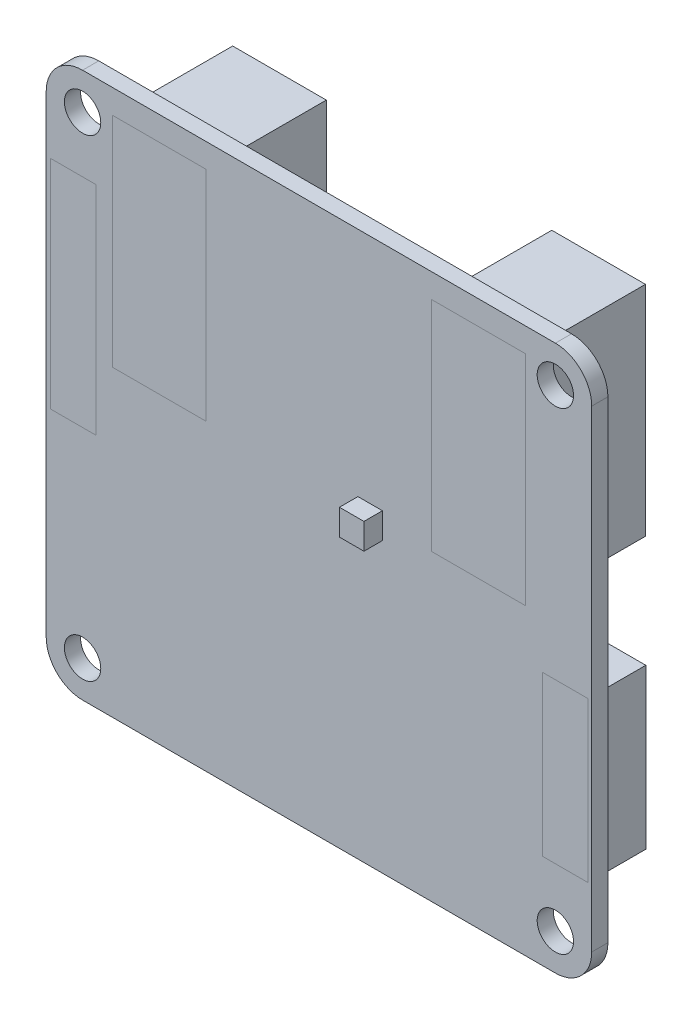
SolidWorks part; units mm, degrees
ref_plane "Front Plane" through (0, 0, 0) normal (0, 0, 1) x (1, 0, 0)
ref_plane "Top Plane" through (0, 0, 0) normal (0, 1, 0) x (1, 0, 0)
ref_plane "Right Plane" through (0, 0, 0) normal (1, 0, 0) x (0, 0, -1)
sketch "Sketch1" plane through (0, 0, 0) normal (0, 0, 1) x (1, 0, 0)
  line L1 (0, 0) -> (60, 0)
  line L2 (0, 0) -> (0, 60)
  line L3 (0, 60) -> (60, 60)
  line L4 (60, 0) -> (60, 60)
  line L5 (7.3, 57.35) -> (17.6, 57.35)
  line L6 (7.3, 57.35) -> (7.3, 33.35)
  line L7 (7.3, 33.35) -> (17.6, 33.35)
  line L8 (17.6, 57.35) -> (17.6, 33.35)
  line L9 (0.4948, 49.84) -> (5.4948, 49.84)
  line L10 (42.4, 57.35) -> (52.7, 57.35)
  line L11 (42.4, 57.35) -> (42.4, 33.35)
  line L12 (42.4, 33.35) -> (52.7, 33.35)
  line L13 (52.7, 57.35) -> (52.7, 33.35)
  line L14 (34.2841, 34.5273) -> (36.9775, 34.5273)
  line L15 (34.2841, 34.5273) -> (34.2841, 31.6832)
  line L16 (34.2841, 31.6832) -> (36.9775, 31.6832)
  line L17 (36.9775, 34.5273) -> (36.9775, 31.6832)
  line L18 (0.4948, 49.84) -> (0.4948, 25.964)
  line L19 (0.4948, 25.964) -> (5.4948, 25.964)
  line L20 (5.4948, 49.84) -> (5.4948, 25.964)
  line L21 (54.5954, 27.94) -> (59.5954, 27.94)
  line L22 (54.5954, 27.94) -> (54.5954, 10.414)
  line L23 (54.5954, 10.414) -> (59.5954, 10.414)
  line L24 (59.5954, 27.94) -> (59.5954, 10.414)
  arc A0 (0, 4) -> (4, 0) centre (4, 4) ccw
  circle A1 centre (4, 4) radius 2
  arc A2 (4, 60) -> (0, 56) centre (4, 56) ccw
  circle A3 centre (4, 56) radius 2
  arc A4 (60, 56) -> (56, 60) centre (56, 56) ccw
  circle A5 centre (56, 56) radius 2
  arc A6 (56, 0) -> (60, 4) centre (56, 4) ccw
  circle A7 centre (56, 4) radius 2
  circle A8 centre (4, 4) radius 4 construction
  circle A9 centre (56, 4) radius 4 construction
  circle A10 centre (56, 56) radius 4 construction
  circle A11 centre (4, 56) radius 4 construction
  point P7 (30, 30)
  point P9 (30, 0)
  point P10 (0, 30)
  point P23 (30, 30)
  dimension "D3" = 8
  dimension "D4" = 4
  dimension "D1" = 60
  dimension "D2" = 60
  dimension "D6" = 10.3
  dimension "D7" = 24
  dimension "D8" = 7.3
  dimension "D9" = 2.65
  dimension "D10" = 7.3
  dimension "D11" = 17.526
  dimension "D12" = 5
  dimension "D13" = 10.414
  dimension "D14" = 23.876
  dimension "D15" = 5
  dimension "D16" = 10.16
  dimension "D5" = 4
extrude "Boss-Extrude1" add sketch "Sketch1" along normal blind 1.778 contours L1 A6 L4 A4 L3 A2 L2 A0 A7 A5 A3 A1 L5 L8 L7 L6 L10 L13 L12 L11 L14 L17 L16 L15 L9 L20 L19 L18 L21 L24 L23 L22 region at (30.2852, 27.3088, 0)
extrude "Boss-Extrude2" add sketch "Sketch1<3>" against normal blind 11.43 and the other way up to surface (1.778 mm away) separate body contours L13 L10 L11 L12 | L8 L5 L6 L7 region at (12.45, 45.35, 0) region at (47.55, 45.35, 0) other way up to face at (58, 4, 1.778)
sketch "Sketch1<3>" plane through (0, 0, 0) normal (0, 0, 1) x (1, 0, 0) same geometry as "Sketch1"
extrude "Boss-Extrude3" add sketch "Sketch1<4>" against normal blind 4.572 and the other way up to surface (1.778 mm away) separate body contours L24 L21 L22 L23 | L20 L9 L18 L19 region at (2.9948, 37.902, 0) region at (57.0954, 19.177, 0) other way up to face at (58, 4, 1.778)
sketch "Sketch1<4>" plane through (0, 0, 0) normal (0, 0, 1) x (1, 0, 0) same geometry as "Sketch1"
extrude "Boss-Extrude5" add sketch "Sketch1<5>" along normal offset from surface (3.81 mm away) 2.032 contours L17 L14 L15 L16 region at (35.6308, 33.1053, 0) up to face at (58, 4, 1.778) offset beyond the face yes
sketch "Sketch1<5>" plane through (0, 0, 0) normal (0, 0, 1) x (1, 0, 0) same geometry as "Sketch1"
